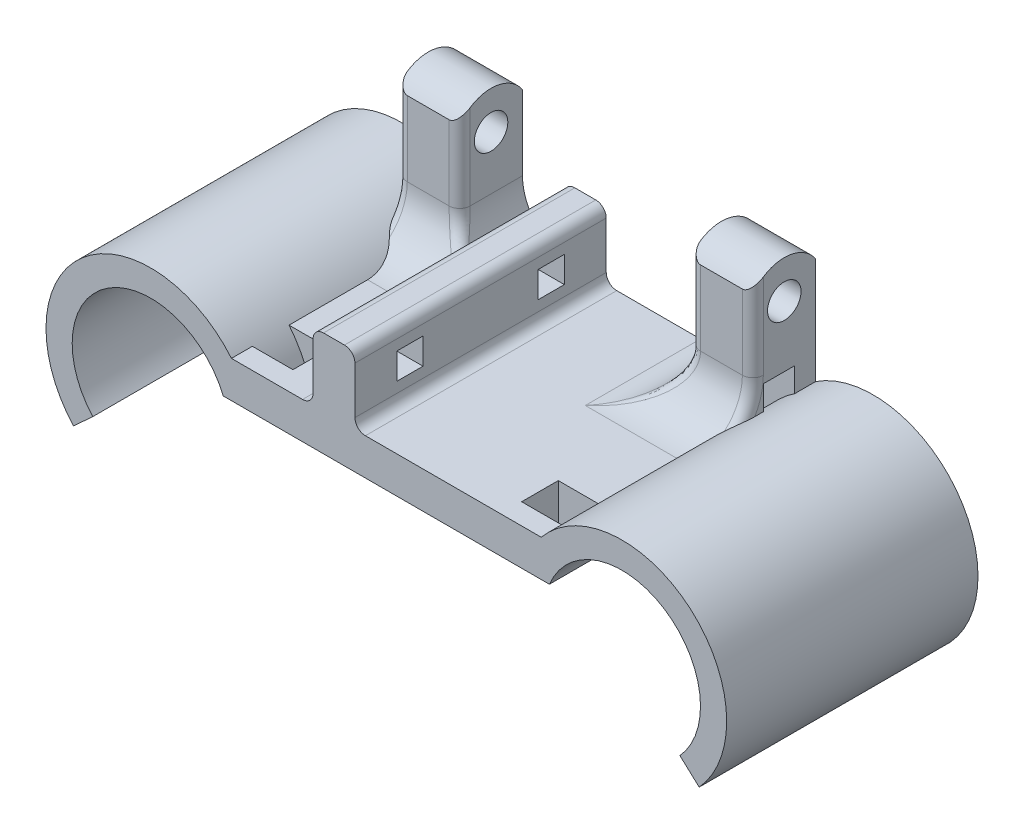
SolidWorks part; units mm, degrees
ref_plane "Front" through (0, 0, 0) normal (0, 0, 1) x (1, 0, 0)
ref_plane "Top" through (0, 0, 0) normal (0, 1, 0) x (1, 0, 0)
ref_plane "Right" through (0, 0, 0) normal (1, 0, 0) x (0, 0, -1)
sketch "Sketch1" plane through (0, 0, 0) normal (0, 0, 1) x (1, 0, 0)
  line L0 (-28.0296, -7.9371) -> (-22.5, -2.8701) construction
  line L1 (-22.5, -2.8701) -> (-15.5709, 0) construction
  line L2 (-22.5, -2.8701) -> (-22.5, 4.6299) construction
  arc A0 (-15.5709, 0) -> (-28.0296, -7.9371) centre (-22.5, -2.8701) ccw
  dimension "D2" = 7.5
  dimension "D1" = 22.5
  dimension "D3" = 200
  dimension "D4" = 67.5
extrude "Extrude-LM8UU Cup" add sketch "Sketch1" along normal blind 24 thin thin type one direction wall 2.5
sketch "Sketch2" plane through (0, 0, 0) normal (0, 0, 1) x (1, 0, 0)
  line L0 (0, 0) -> (-15.5709, 0)
extrude "Extrude-Straight" add sketch "Sketch2" along normal through all thin thin type one direction wall 3.5
sketch "Sketch5" plane through (0, 0, 24) normal (0, 0, 1) x (1, 0, 0)
  line L0 (0, 0) -> (-15.5709, 0) construction
  line L1 (-12.9207, 0) -> (-10.9207, 0)
  line L2 (-10.9207, 0) -> (-10.9207, 3.5)
  line L3 (0, 3.5) -> (-14.7915, 3.5) construction
  line L4 (-10.9207, 3.5) -> (-14.7915, 3.5)
  arc A0 (-14.7915, 3.5) -> (-12.9207, 0) centre (-22.5, -2.8701) cw
  arc A1 (-14.7915, 3.5) -> (-29.8728, -9.626) centre (-22.5, -2.8701) ccw construction
  dimension "D1" = 2
extrude "Cut-Upper Zip Tie" cut sketch "Sketch5" against normal blind 3.5 from offset 2 offset against normal yes
mirror "Mirror-Cup And Straight" about plane through (0, 0, 0) normal (1, 0, 0) of "Extrude-LM8UU Cup", "Extrude-Straight", "Cut-Upper Zip Tie"
sketch "Sketch6" plane through (0, 0, 0) normal (1, 0, 0) x (0, 0, -1)
  line L1 (-6, 3.5) -> (0, 3.5)
  line L2 (-6, 3.5) -> (-6, 15.6299)
  line L3 (-6, 15.6299) -> (0, 15.6299)
  line L4 (0, 3.5) -> (0, 15.6299)
  dimension "D1" = 6
  dimension "D2" = 18.5
extrude "Boss-Rod Attachments" add sketch "Sketch6" along normal blind 6 from offset 11
sketch "Sketch7" plane through (11, 0, 0) normal (-1, 0, 0) x (0, 0, 1)
  line L0 (3, 15.6299) -> (3, 13.6299) construction
  line L1 (0, 15.6299) -> (6, 15.6299) construction
  circle A0 centre (3, 13.6299) radius 1.6
  dimension "D2" = 3.2
  dimension "D1" = 16.5
extrude "Cut-Rod Screw Hole" cut sketch "Sketch7" against normal through all
sketch "Sketch8" plane through (11, 0, 0) normal (-1, 0, 0) x (0, 0, 1)
  line L0 (0, 15.6299) -> (6, 15.6299)
  arc A0 (0, 15.6299) -> (6, 15.6299) centre (3, 13.6299) cw
  circle A1 centre (3, 13.6299) radius 1.6 construction
extrude "Boss-Rod Round End" add sketch "Sketch8" against normal up to surface (6 mm away) up to face at (17, 13.6299, 4.6)
mirror "Mirror-Rod Attachment" about plane through (0, 0, 0) normal (1, 0, 0) of "Boss-Rod Round End", "Cut-Rod Screw Hole", "Boss-Rod Attachments"
fillet "Fillet1" radius 5 4 edges at (12.8957, 3.5, 6) (-12.8957, 3.5, 6) (-11, 3.5, 3) (11, 3.5, 3)
fillet "Fillet2" radius 1 7 edges at (9.5355, 4.9645, 7.4645) (-9.5355, 4.9645, 7.4645) (11, 12.0649, 6) (-11, 12.0649, 6) (17, 6.9079, 6.2603) (-17, 12.0649, 6) (17, 12.0649, 6)
sketch "Sketch9" plane through (0, 0, 0) normal (1, 0, 0) x (0, 0, -1)
  line L1 (0, 0) -> (-24, 0)
  line L2 (0, 0) -> (0, 10)
  line L3 (0, 10) -> (-24, 10)
  line L4 (-24, 0) -> (-24, 10)
  dimension "D1" = 10
extrude "Boss-Spectra Mount" add sketch "Sketch9" against normal blind 4 from offset 3 offset against normal yes
sketch "Sketch10" plane through (-7, 0, 0) normal (-1, 0, 0) x (0, 0, 1)
  line L1 (17.5, 8) -> (20, 8)
  line L2 (17.5, 8) -> (17.5, 5.5)
  line L3 (17.5, 5.5) -> (20, 5.5)
  line L4 (20, 8) -> (20, 5.5)
  line L5 (24, 10) -> (24, 3.5) construction
  line L6 (11, 3.5) -> (24, 3.5) construction
  dimension "D1" = 2.5
  dimension "D2" = 2
  dimension "D3" = 4
extrude "Cut-Spectra Hole" cut sketch "Sketch10" against normal up to surface (4 mm away) up to face at (-3, 6.75, 12)
pattern_linear "LPattern-Spectra Holes" count 1 spacing 4 along (0, 1, 0) count 2 spacing 13.5 along (0, 0, -1) of "Cut-Spectra Hole"
fillet "Fillet3" radius 1 7 edges at (-7, 3.601, 4.9) (-7, 3.5175, 10.5819) (-7, 3.5, 17.5) (-3, 3.5, 12) (-3, 10, 12) (-7, 10, 12)
sketch "Sketch11" plane through (0, 0, 0) normal (0, 0, -1) x (-1, 0, 0)
  line L0 (-17, 5.4815) -> (-17, 15.6299) construction
  line L1 (-15.5709, 0) -> (15.5709, 0) construction
  line L2 (-17, 7.7952) -> (-21.7869, 7.1044)
  line L3 (-12.9207, 0) -> (-10.8483, 0)
  arc A0 (-12.9207, 0) -> (-14.7915, 3.5) centre (-22.5, -2.8701) ccw construction
  arc A1 (-12.9207, 0) -> (-21.7869, 7.1044) centre (-22.5, -2.8701) ccw
  arc A2 (-10.8483, 0) -> (-17, 7.7952) centre (-22.5, -2.8701) ccw
  arc A3 (-11.0049, 0.574) -> (-21.6442, 9.0993) centre (-22.5, -2.8701) ccw construction
  arc A4 (-17, 5.4815) -> (-29.8728, -9.626) centre (-22.5, -2.8701) ccw construction
  dimension "D1" = 2
extrude "Cut-Lower Zip Tie" cut sketch "Sketch11" against normal blind 3 from offset 2 offset against normal yes
mirror "Mirror-Lower Zip Tie" about plane through (0, 0, 0) normal (1, 0, 0) of "Cut-Lower Zip Tie"
sketch "Sketch13" plane through (0, 0, 0) normal (0, 0, -1) x (-1, 0, 0)
  circle A0 centre (0, 13) radius 3.5
  dimension "D1" = 7
  dimension "D2" = 13
extrude "Boss-Magnet Boss" [suppressed] add sketch "Sketch13" against normal blind 3.5
sketch "Sketch12" [suppressed] plane through (0, 0, 0) normal (0, 0, -1) x (-1, 0, 0)
  circle A0 centre (0, 13) radius 2.5
  arc A1 (2.8723, 15) -> (0, 9.5) centre (0, 13) ccw construction
  dimension "D1" = 5
extrude "Cut-Magnet Slot" [suppressed] cut sketch "Sketch12" against normal blind 2.5
